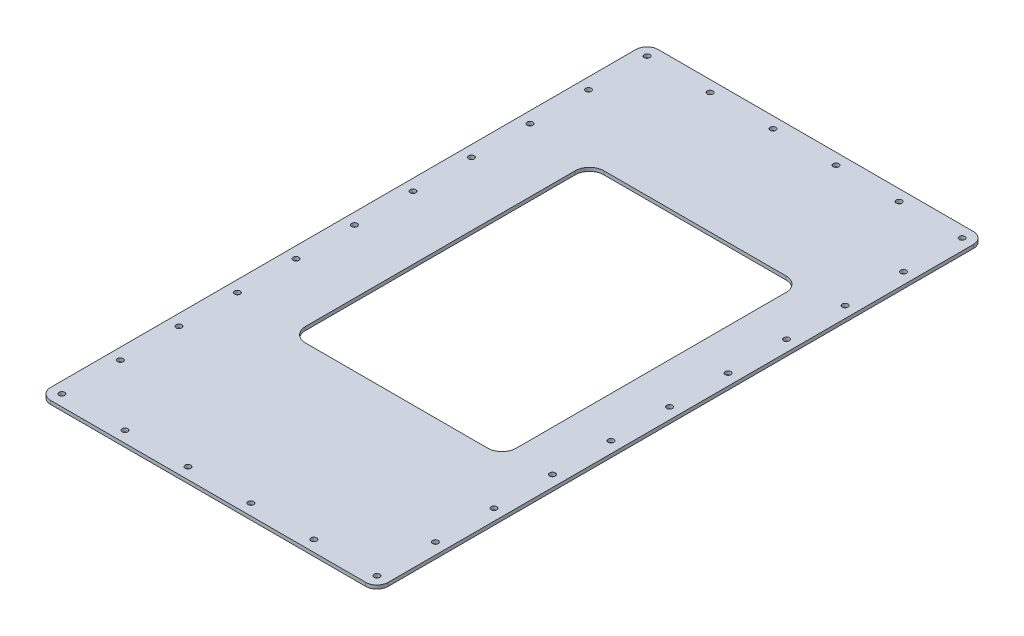
SolidWorks part; units mm, degrees
material "5052-H32"
ref_plane "Front Plane" through (0, 0, 0) normal (0, 0, 1) x (1, 0, 0)
ref_plane "Top Plane" through (0, 0, 0) normal (0, 1, 0) x (1, 0, 0)
ref_plane "Right Plane" through (0, 0, 0) normal (1, 0, 0) x (0, 0, -1)
sketch "Sketch9" plane through (0, 0, 0) normal (0, 1, 0) x (1, 0, 0)
  line L0 (-150, 0) -> (-150, 540)
  line L13 (-150, 540) -> (150, 540)
  line L14 (103.6625, 157.4438) -> (-83.6625, 157.4438)
  line L19 (150, 540) -> (150, 0)
  line L20 (103.6625, 157.4438) -> (103.6625, 422.5563)
  line L21 (103.6625, 422.5563) -> (-83.6625, 422.5563)
  line L22 (-83.6625, 157.4438) -> (-83.6625, 422.5563)
  line L23 (103.6625, 290) -> (-83.6625, 290) construction
  line L24 (10, 422.5562) -> (10, 157.4438) construction
  line L25 (-150, 0) -> (150, 0)
  point P8 (0, 0)
  point P19 (0, 0)
  dimension "D3" = 265.1125
  dimension "D4" = 187.325
  dimension "D1" = 300
  dimension "D2" = 540
  dimension "D6" = 140
  dimension "D5" = 250
extrude "Boss-Extrude7" add sketch "Sketch9" along normal blind 3.175 separate body contours L0 L25 L19 L13 L14 L22 L21 L20 region at (-143.8226, 0, -270)
fillet "Fillet4" radius 10 4 edges at (-150, 1.5875, -540) (150, 1.5875, -540) (-150, 1.5875, 0) (150, 1.5875, 0)
fillet "Fillet5" radius 12.7 4 edges at (-83.6625, 1.5875, -157.4438) (103.6625, 1.5875, -157.4438) (103.6625, 1.5875, -422.5563) (-83.6625, 1.5875, -422.5563)
sketch "Sketch10" plane through (0, 3.175, 0) normal (0, 1, 0) x (1, 0, 0)
  line L0 (-150, 10) -> (-150, 530) construction
  line L1 (-140, 0) -> (140, 0) construction
  circle A0 centre (-140, 10) radius 2.5
  circle A1 centre (-84, 10) radius 2.5
  circle A2 centre (-28, 10) radius 2.5
  circle A3 centre (28, 10) radius 2.5
  circle A4 centre (84, 10) radius 2.5
  circle A5 centre (140, 10) radius 2.5
  circle A10 centre (140, 62) radius 2.5
  circle A15 centre (140, 114) radius 2.5
  circle A20 centre (140, 166) radius 2.5
  circle A25 centre (140, 218) radius 2.5
  circle A30 centre (140, 270) radius 2.5
  circle A35 centre (140, 322) radius 2.5
  circle A40 centre (140, 374) radius 2.5
  circle A45 centre (140, 426) radius 2.5
  circle A50 centre (140, 478) radius 2.5
  circle A51 centre (-84, 530) radius 2.5
  circle A52 centre (-28, 530) radius 2.5
  circle A53 centre (28, 530) radius 2.5
  circle A54 centre (84, 530) radius 2.5
  circle A55 centre (140, 530) radius 2.5
  circle A56 centre (-140, 62) radius 2.5
  circle A57 centre (-140, 114) radius 2.5
  circle A58 centre (-140, 166) radius 2.5
  circle A59 centre (-140, 218) radius 2.5
  circle A60 centre (-140, 270) radius 2.5
  circle A61 centre (-140, 322) radius 2.5
  circle A62 centre (-140, 374) radius 2.5
  circle A63 centre (-140, 426) radius 2.5
  circle A64 centre (-140, 478) radius 2.5
  circle A65 centre (-140, 530) radius 2.5
  circle A66 centre (-84, 62) radius 2.5 [skipped]
  circle A67 centre (-28, 62) radius 2.5 [skipped]
  circle A68 centre (28, 62) radius 2.5 [skipped]
  circle A69 centre (84, 62) radius 2.5 [skipped]
  circle A70 centre (-84, 114) radius 2.5 [skipped]
  circle A71 centre (-28, 114) radius 2.5 [skipped]
  circle A72 centre (28, 114) radius 2.5 [skipped]
  circle A73 centre (84, 114) radius 2.5 [skipped]
  circle A74 centre (-84, 166) radius 2.5 [skipped]
  circle A75 centre (-28, 166) radius 2.5 [skipped]
  circle A76 centre (28, 166) radius 2.5 [skipped]
  circle A77 centre (84, 166) radius 2.5 [skipped]
  circle A78 centre (-84, 218) radius 2.5 [skipped]
  circle A79 centre (-28, 218) radius 2.5 [skipped]
  circle A80 centre (28, 218) radius 2.5 [skipped]
  circle A81 centre (84, 218) radius 2.5 [skipped]
  circle A82 centre (-84, 270) radius 2.5 [skipped]
  circle A83 centre (-28, 270) radius 2.5 [skipped]
  circle A84 centre (28, 270) radius 2.5 [skipped]
  circle A85 centre (84, 270) radius 2.5 [skipped]
  circle A86 centre (-84, 322) radius 2.5 [skipped]
  circle A87 centre (-28, 322) radius 2.5 [skipped]
  circle A88 centre (28, 322) radius 2.5 [skipped]
  circle A89 centre (84, 322) radius 2.5 [skipped]
  circle A90 centre (-84, 374) radius 2.5 [skipped]
  circle A91 centre (-28, 374) radius 2.5 [skipped]
  circle A92 centre (28, 374) radius 2.5 [skipped]
  circle A93 centre (84, 374) radius 2.5 [skipped]
  circle A94 centre (-84, 426) radius 2.5 [skipped]
  circle A95 centre (-28, 426) radius 2.5 [skipped]
  circle A96 centre (28, 426) radius 2.5 [skipped]
  circle A97 centre (84, 426) radius 2.5 [skipped]
  circle A98 centre (-84, 478) radius 2.5 [skipped]
  circle A99 centre (-28, 478) radius 2.5 [skipped]
  circle A100 centre (28, 478) radius 2.5 [skipped]
  circle A101 centre (84, 478) radius 2.5 [skipped]
  dimension "D1" = 5
  dimension "D2" = 10
  dimension "D3" = 10
  dimension "D6" = 52
  dimension "D7" = 56
  dimension "D4" = 6
  dimension "D5" = 11
extrude "Cut-Extrude1" cut sketch "Sketch10" against normal up to next (3.175 mm away)
equation "\"W\"= 260"
equation "\"L\"= 500"
equation "\"Offset\"= 20"
equation "\"H\"= 110"
equation "\"Compartment Width\"= 90"
equation "\"T\"= 4.7625 * 2 / 3"
equation "\"Inside Fillet Radius\"= 10"
equation "\"Hole\"=15"
equation "\"Wheel to Wall\"= \"Compartment Width\" / 2"
equation "\"D1@Sketch9\"=\"W\"+40"
equation "\"D2@Sketch9\"=\"L\"+40"
equation "\"D6@Sketch10\"=(\"L\"+20)/10"
equation "\"D7@Sketch10\"=(\"W\"+20)/5"
equation "\"D5@Sketch9\"=(\"L\"/2+20)-\"Offset\""
